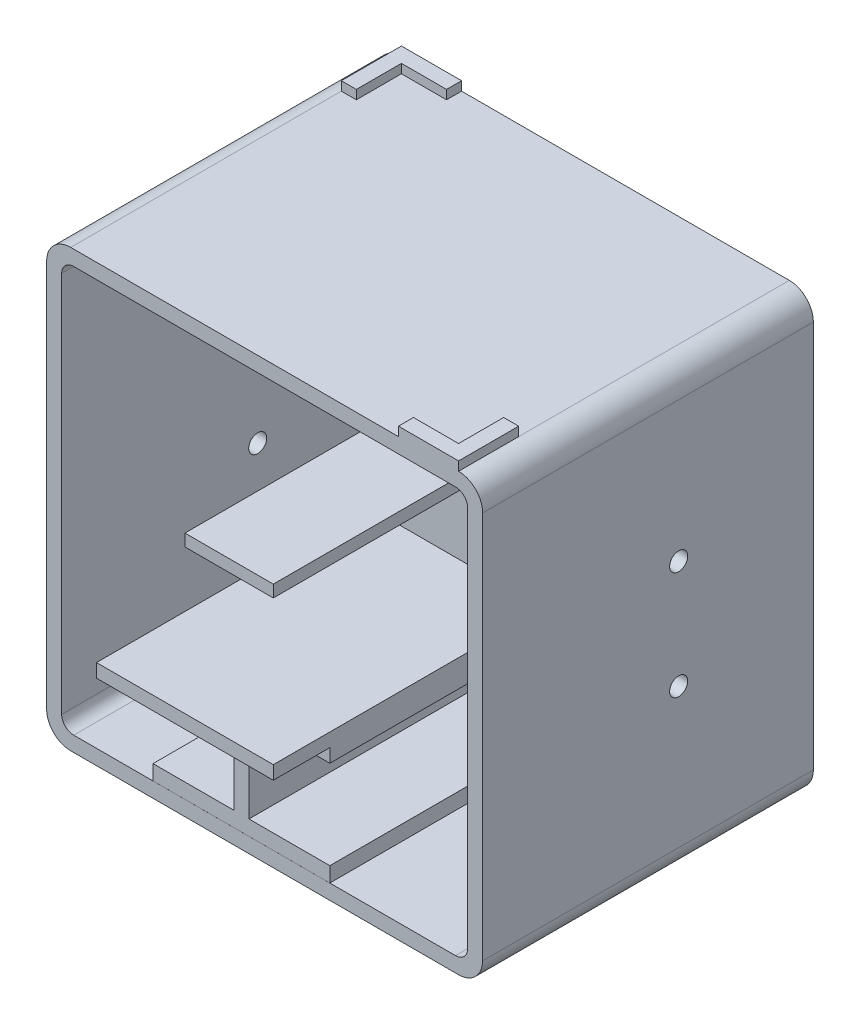
SolidWorks part; units mm, degrees
ref_plane "Front Plane" through (0, 0, 0) normal (0, 0, 1) x (1, 0, 0)
ref_plane "Top Plane" through (0, 0, 0) normal (0, 1, 0) x (1, 0, 0)
ref_plane "Right Plane" through (0, 0, 0) normal (1, 0, 0) x (0, 0, -1)
sketch "Sketch1" plane through (0, 0, 0) normal (0, 0, 1) x (1, 0, 0)
  line L0 (-33.75, -33.75) -> (33.75, -33.75) construction
  line L1 (-31.75, 33.75) -> (31.75, 33.75)
  line L2 (-33.75, 31.75) -> (-33.75, -31.75)
  line L3 (-31.75, -33.75) -> (31.75, -33.75)
  line L4 (33.75, 31.75) -> (33.75, -31.75)
  line L5 (-36.25, 32.25) -> (-36.25, -32.25)
  line L6 (33.75, 33.75) -> (33.75, -33.75) construction
  line L7 (-32.25, -36.25) -> (32.25, -36.25)
  line L8 (36.25, 32.25) -> (36.25, -32.25)
  line L9 (-32.25, 36.25) -> (32.25, 36.25)
  line L10 (-36.25, 36.25) -> (-36.25, -36.25) construction
  line L11 (-36.25, 36.25) -> (36.25, 36.25) construction
  line L12 (-33.75, 33.75) -> (33.75, 33.75) construction
  line L13 (-33.75, 33.75) -> (-33.75, -33.75) construction
  line L14 (-36.25, -36.25) -> (36.25, -36.25) construction
  line L15 (36.25, 36.25) -> (36.25, -36.25) construction
  line L16 (55, 0) -> (-55, 0) construction
  line L17 (0, -55) -> (0, 55) construction
  arc A0 (-36.25, 32.25) -> (-32.25, 36.25) centre (-32.25, 32.25) cw
  arc A1 (-31.75, 33.75) -> (-33.75, 31.75) centre (-31.75, 31.75) ccw
  arc A2 (-33.75, -31.75) -> (-31.75, -33.75) centre (-31.75, -31.75) ccw
  arc A3 (31.75, -33.75) -> (33.75, -31.75) centre (31.75, -31.75) ccw
  arc A4 (31.75, 33.75) -> (33.75, 31.75) centre (31.75, 31.75) cw
  arc A5 (-36.25, -32.25) -> (-32.25, -36.25) centre (-32.25, -32.25) ccw
  arc A6 (32.25, -36.25) -> (36.25, -32.25) centre (32.25, -32.25) ccw
  arc A7 (36.25, 32.25) -> (32.25, 36.25) centre (32.25, 32.25) ccw
  point P36 (-33.75, 0)
  point P39 (0, 33.75)
  dimension "D3" = 4
  dimension "D4" = 2
  dimension "D5" = 2
  dimension "D6" = 4
  dimension "D1" = 67.5
  dimension "D2" = 2.5
extrude "Boss-Extrude1" add sketch "Sketch1" along normal blind 55
sketch "Sketch2" plane through (0, 0, 0) normal (0, 0, 1) x (1, 0, 0)
  line L1 (-33.75, 33.75) -> (33.75, 33.75)
  line L2 (-33.75, 33.75) -> (-33.75, -33.75)
  line L3 (-33.75, -33.75) -> (33.75, -33.75)
  line L4 (33.75, 33.75) -> (33.75, -33.75)
extrude "Boss-Extrude2" add sketch "Sketch2" along normal blind 2.5
sketch "Sketch3" plane through (0, 0, 2.5) normal (0, 0, 1) x (1, 0, 0)
  line L0 (-4.38, 17.29) -> (-18.88, 12.29) construction
  line L1 (-19.88, 11.29) -> (-3.38, 11.29)
  line L2 (-18.88, 12.29) -> (-4.38, 12.29) construction
  line L3 (-18.88, 12.29) -> (-18.88, 17.29) construction
  line L4 (-18.88, 17.29) -> (-4.38, 17.29) construction
  line L5 (-4.38, 12.29) -> (-4.38, 17.29) construction
  line L6 (-3.38, 11.29) -> (-3.38, 18.29)
  line L7 (-19.88, 18.29) -> (-3.38, 18.29)
  line L8 (-19.88, 11.29) -> (-19.88, 18.29)
  line L9 (-36.25, 32.25) -> (-36.25, -32.25) construction
  line L10 (-3, -7) -> (3, -7) construction
  line L11 (-3, -7) -> (-3, 7) construction
  line L12 (-3, 7) -> (3, 7) construction
  line L13 (3, -7) -> (3, 7) construction
  line L14 (-3, -7) -> (3, 7) construction
  line L15 (-3, 7) -> (3, -7) construction
  line L16 (32.25, 36.25) -> (-32.25, 36.25) construction
  line L17 (-4, -8) -> (-4, 8)
  line L18 (-4, 8) -> (4, 8)
  line L19 (4, -8) -> (4, 8)
  line L20 (-4, -8) -> (4, -8)
  line L21 (-18.88, 17.29) -> (-4.38, 12.29) construction
  point P0 (0, 0)
  dimension "D2" = 6
  dimension "D3" = 14
  dimension "D5" = 14.5
  dimension "D6" = 5
  dimension "D7" = 16.37
  dimension "D8" = 23.96
  dimension "D1" = 1
  dimension "D4" = 1
extrude "Cut-Extrude1" cut sketch "Sketch3" against normal up to next
fillet "Fillet1" radius 1 8 edges at (-19.88, 11.29, 1.25) (-19.88, 18.29, 1.25) (-3.38, 18.29, 1.25) (-3.38, 11.29, 1.25) (4, -8, 1.25) (-4, -8, 1.25) (-4, 8, 1.25) (4, 8, 1.25)
sketch "Sketch4" plane through (0, 0, 0) normal (0, 0, -1) x (-1, 0, 0)
  line L0 (-32.25, 36.25) -> (32.25, 36.25) construction
  line L1 (-36.25, -32.25) -> (-36.25, 32.25) construction
  circle A0 centre (-28.75, 28.75) radius 1.5
  dimension "D3" = 3
  dimension "D1" = 7.5
  dimension "D2" = 7.5
extrude "Cut-Extrude2" cut sketch "Sketch4" against normal up to next
mirror "Mirror1" about plane through (0, 0, 0) normal (1, 0, 0) of "Cut-Extrude2"
mirror "Mirror2" about plane through (0, 0, 0) normal (0, 1, 0) of "Mirror1"
sketch "Sketch5" plane through (0, 0, 0) normal (1, 0, 0) x (0, 0, -1)
  line L0 (-17.3967, 14) -> (-64.3967, 14)
  line L1 (-19.3967, 12) -> (-62.3967, 12)
  line L2 (-19.3967, 12) -> (-19.3967, -12)
  line L3 (-19.3967, -12) -> (-62.3967, -12)
  line L5 (-64.3967, 14) -> (-64.3967, 12)
  line L6 (-17.3967, -14) -> (-64.3967, -14)
  line L7 (-17.3967, 14) -> (-17.3967, -14)
  line L8 (-62.3967, 12) -> (-64.3967, 12)
  line L9 (-62.3967, -12) -> (-64.3967, -12)
  line L10 (-64.3967, -12) -> (-64.3967, -14)
  line L11 (-62.3967, 12) -> (-62.3967, -12) construction
  line L12 (-64.3967, 14) -> (-64.3967, -14) construction
  line L13 (30.25, 0) -> (-30.25, 0) construction
  point P4 (-67.3967, 9.4093)
  point P6 (-63.4797, -14.5907)
  point P11 (-65.5121, -14.5907)
  point P13 (0, 0)
  point P14 (-17.3967, 11.4093)
  point P15 (0, 0)
  dimension "D1" = 43
  dimension "D2" = 24
  dimension "D4" = 12
  dimension "D3" = 2
extrude "Boss-Extrude3" add sketch "Sketch5" along normal blind 10.84 and the other way blind 18.56 separate body
sketch "Sketch6" plane through (0, 0, 64.3967) normal (0, 0, 1) x (1, 0, 0)
  line L0 (-18.56, -14) -> (10.84, -14) construction
  line L1 (-18.56, -14) -> (10.84, -14)
  line L2 (-18.56, -14) -> (-18.56, -16.5)
  line L3 (-18.56, -16.5) -> (-5.11, -16.5)
  line L4 (10.84, -14) -> (10.84, -16.5)
  line L5 (-31.75, -33.75) -> (31.75, -33.75) construction
  line L6 (-18.56, -33.75) -> (10.84, -33.75)
  line L7 (-18.56, -33.75) -> (-18.56, -31.25)
  line L8 (-18.56, -31.25) -> (-5.11, -31.25)
  line L9 (10.84, -33.75) -> (10.84, -31.25)
  line L10 (-2.61, -16.5) -> (10.84, -16.5)
  line L12 (-5.11, -16.5) -> (-5.11, -31.25)
  line L14 (-2.61, -16.5) -> (-2.61, -31.25)
  line L15 (-2.61, -31.25) -> (10.84, -31.25)
  line L16 (-18.56, -12) -> (-18.56, -14) construction
  point P16 (0, 0)
  point P17 (0, 0)
  dimension "D1" = 2.5
  dimension "D2" = 2.5
  dimension "D3" = 29.4
  dimension "D4" = 29.4
  dimension "D5" = 2.5
  dimension "D6" = 13.45
  dimension "D7" = 13.45
extrude "Boss-Extrude4" add sketch "Sketch6" against normal blind 47
sketch "Sketch7" plane through (0, 0, 64.3967) normal (0, 0, 1) x (1, 0, 0)
  line L0 (-18.56, -12) -> (-18.56, -16.5) construction
  line L1 (-18.56, -14.25) -> (10.84, -14.25)
  line L2 (-18.56, -14.25) -> (-18.56, -33.75)
  line L3 (-18.56, -33.75) -> (10.84, -33.75)
  line L4 (10.84, -14.25) -> (10.84, -33.75)
  line L5 (10.84, -33.75) -> (31.75, -33.75) construction
  line L6 (10.84, -33.75) -> (10.84, -31.25) construction
extrude "Cut-Extrude3" cut sketch "Sketch7" against normal blind 9.4
sketch "Sketch8" plane through (-18.56, 0, 0) normal (-1, 0, 0) x (0, 0, 1)
  line L0 (19.3967, 12) -> (19.3967, -12) construction
  line L1 (19.3967, 12) -> (24.8967, 12)
  line L2 (19.3967, 12) -> (19.3967, 6.5)
  line L3 (19.3967, 6.5) -> (23.2967, 6.5)
  line L4 (24.8967, 12) -> (24.8967, 8.1)
  arc A0 (23.2967, 6.5) -> (24.8967, 8.1) centre (23.2967, 8.1) ccw
  circle A1 centre (22.3967, 9) radius 1 construction
  circle A2 centre (22.3967, 9) radius 1.8
  point P9 (22.0532, 9.3436)
  point P10 (0, 0)
  dimension "D1" = 1.6
  dimension "D4" = 3.6
  dimension "D5" = 2
  dimension "D2" = 5.5
  dimension "D3" = 5.5
  dimension "D6" = 3
  dimension "D7" = 3
extrude "Boss-Extrude5" add sketch "Sketch8" against normal blind 3
sketch "Sketch9" plane through (-15.56, 0, 0) normal (-1, 0, 0) x (0, 0, 1)
  circle A0 centre (22.3967, 9) radius 1
  circle A1 centre (22.3967, 9) radius 2
  point P3 (0, 0)
  point P4 (22.3968, 6.4093)
  point P5 (21.7274, 9.3701)
  point P6 (21.8928, 9.3778)
  point P7 (22.0532, 9.3436)
  dimension "D1" = 2
  dimension "D2" = 1
extrude "Boss-Extrude6" add sketch "Sketch9" along normal blind 1.5
ref_plane "Plane1" through (-3.86, 0, 0) normal (-1, 0, 0) x (0, 0, 1)
mirror "Mirror3" about plane through (-3.86, 0, 0) normal (-1, 0, 0) of "Boss-Extrude6", "Boss-Extrude5"
ref_plane "Plane2" through (0, 0, 0) normal (0, 1, 0) x (1, 0, 0)
mirror "Mirror4" about plane through (0, 0, 0) normal (0, 1, 0) of "Mirror3"
sketch "Sketch10" plane through (-36.25, 0, 0) normal (-1, 0, 0) x (0, 0, 1)
  circle A0 centre (22.3967, 9) radius 1.5
  circle A1 centre (22.3967, -9) radius 1.5
  dimension "D1" = 3
  dimension "D2" = 3
extrude "Cut-Extrude4" cut sketch "Sketch10" against normal through all
sketch "Sketch11" plane through (0, 14, 0) normal (0, 1, 0) x (1, 0, 0)
  line L1 (-18.56, -64.3967) -> (-3.86, -64.3967)
  line L2 (-18.56, -64.3967) -> (-18.56, -24.8967)
  line L3 (-15.56, -19.3967) -> (-3.86, -19.3967)
  line L4 (-3.86, -64.3967) -> (-3.86, -19.3967)
  line L5 (-15.56, -19.3967) -> (7.84, -19.3967) construction
  line L8 (-15.56, -19.3967) -> (-15.56, -24.8967)
  line L9 (-15.56, -24.8967) -> (-18.56, -24.8967)
  point P2 (0, 0)
  point P5 (0, 0)
  point P7 (-20.0738, -64.5243)
  point P12 (-18.56, -64.3967)
  dimension "D1" = 3
  dimension "D2" = 5.5
extrude "Cut-Extrude5" cut sketch "Sketch11" against normal blind 2
sketch "Sketch12" plane through (0, 36.25, 0) normal (0, 1, 0) x (1, 0, 0)
  line L0 (-32.25, -55) -> (-32.25, 0) construction
  line L1 (32.25, -55) -> (29.75, -55)
  line L2 (32.25, -55) -> (32.25, -45)
  line L3 (32.25, -45) -> (29.75, -45)
  line L4 (29.75, -52.5) -> (29.75, -45)
  line L5 (32.25, -55) -> (22.25, -55)
  line L6 (32.25, -55) -> (32.25, -52.5)
  line L7 (29.75, -52.5) -> (22.25, -52.5)
  line L8 (22.25, -55) -> (22.25, -52.5)
  line L10 (-32.25, 0) -> (-32.25, -10)
  line L11 (-32.25, -10) -> (-29.75, -10)
  line L12 (-29.75, -2.5) -> (-29.75, -10)
  line L13 (-32.25, 0) -> (-22.25, 0)
  line L15 (-29.75, -2.5) -> (-22.25, -2.5)
  line L16 (-22.25, 0) -> (-22.25, -2.5)
  point P12 (0, 0)
  point P14 (0, 0)
  point P17 (-48.3846, -13.7532)
  point P18 (-47.2394, -13.4317)
  point P19 (-46.2147, -7.6654)
  point P20 (0, 0)
  point P21 (-30.2268, -3.3671)
  point P22 (-16.3138, -10.0187)
  point P23 (-32.25, 0)
  point P26 (-32.25, -9.858)
  point P27 (-32.25, 0)
  line M6 (-32.25, -55) -> (32.25, -55)
  line M7 (32.25, -55) -> (32.25, 0)
  dimension "D1" = 2.5
  dimension "D2" = 10
  dimension "D3" = 2.5
  dimension "D4" = 10
  dimension "D5" = 2.5
extrude "Boss-Extrude7" add sketch "Sketch12" along normal blind 1.5 contours L8 L2 L3 L4 L7 M6 M7 | L10 L11 L12 L15 L16 L13 region at (31, 36.25, 54.8586)
